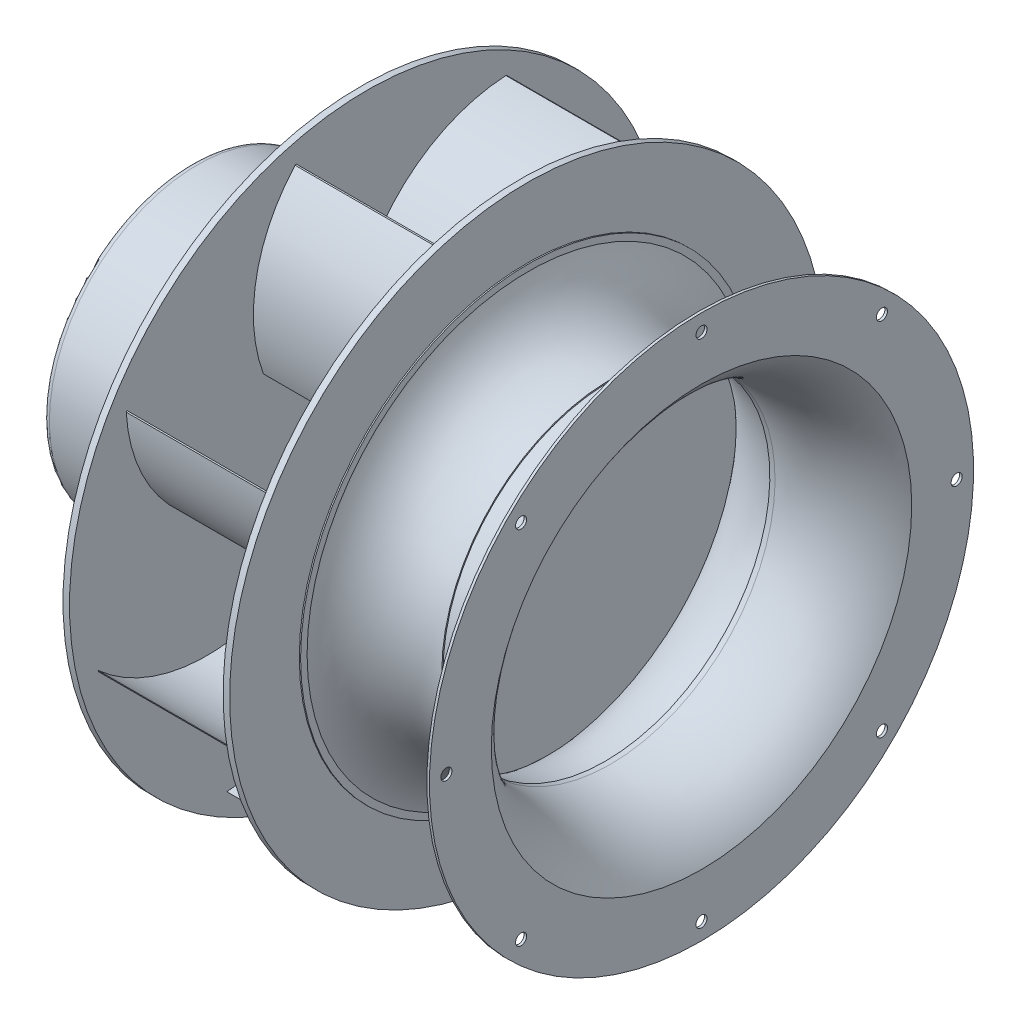
SolidWorks part; units mm, degrees
ref_plane "Front Plane" through (0, 0, 0) normal (0, 0, 1) x (1, 0, 0)
ref_plane "Top Plane" through (0, 0, 0) normal (0, 1, 0) x (1, 0, 0)
ref_plane "Right Plane" through (0, 0, 0) normal (1, 0, 0) x (0, 0, -1)
sketch "Sketch1" plane through (0, 0, 0) normal (0, 0, 1) x (1, 0, 0)
  line L0 (0, 0) -> (831.9083, 0) construction
  line L1 (0, 0) -> (0, 109)
  line L2 (5, 114) -> (70, 114)
  line L3 (70, 114) -> (70, 138)
  line L4 (70, 138) -> (90, 138)
  line L5 (90, 138) -> (90, 98)
  line L6 (90, 98) -> (95, 98)
  line L7 (95, 98) -> (95, 133)
  line L8 (95, 133) -> (105, 133)
  line L9 (105, 133) -> (105, 98)
  line L10 (105, 98) -> (130, 98)
  line L11 (130, 98) -> (130, 0)
  line L12 (130, 0) -> (0, 0)
  arc A0 (5, 114) -> (0, 109) centre (5, 109) ccw
  point P16 (0, 114)
  dimension "D10" = 5
  dimension "D1" = 114
  dimension "D2" = 24
  dimension "D3" = 70
  dimension "D4" = 40
  dimension "D5" = 35
  dimension "D6" = 5
  dimension "D7" = 20
  dimension "D8" = 10
  dimension "D9" = 60
revolve "Revolve1" add sketch "Sketch1" angle 360 about L0
sketch "Sketch2" plane through (130, 0, 0) normal (1, 0, 0) x (0, 0, -1)
  circle A0 centre (0, 0) radius 228.5
  dimension "D1" = 457
extrude "Extrude1" add sketch "Sketch2" along normal blind 5
sketch "Sketch9" plane through (130, 0, 0) normal (-1, 0, 0) x (0, 0, 1)
  circle A0 centre (0, 0) radius 223.5
  circle A1 centre (0, 0) radius 100
  circle A2 centre (0, 0) radius 228.5 construction
  dimension "D1" = 5
  dimension "D2" = 200
extrude "Extrude7" cut sketch "Sketch9" against normal blind 3
ref_plane "Plane1" through (253, 0, 0) normal (1, 0, 0) x (0, 0, -1)
sketch "Sketch3" plane through (253, 0, 0) normal (1, 0, 0) x (0, 0, -1)
  circle A0 centre (0, 0) radius 228.5
  dimension "D1" = 457
extrude "Extrude2" add sketch "Sketch3" along normal blind 5 separate body
sketch "Sketch4" plane through (135, 0, 0) normal (1, 0, 0) x (0, 0, -1)
  line L0 (0, 0) -> (0, 213.5) construction
  line L1 (0, 0) -> (114.25, 197.8868) construction
  line L2 (0, 112.5) -> (0.866, 112)
  line L3 (106.75, 184.8964) -> (107.616, 184.3964)
  circle A0 centre (0, 0) radius 213.5 construction
  circle A1 centre (0, 0) radius 228.5 construction
  circle A2 centre (0, 0) radius 112.5 construction
  arc A3 (0, 112.5) -> (106.75, 184.8964) centre (113.4764, 60.0775) cw
  arc A4 (0.866, 112) -> (107.616, 184.3964) centre (114.3424, 59.5775) cw
  dimension "D1" = 15
  dimension "D2" = 225
  dimension "D6" = 125
  dimension "D7" = 125
  dimension "D3" = 30
  dimension "D4" = 60
  dimension "D5" = 1
extrude "Extrude3" add sketch "Sketch4" along normal up to surface (123 mm away) up to face at (258, 0, -228.5)
ref_axis "Axis1" through (253.5503, 0, 0) along (-1, 0, 0)
pattern_circular "CirPattern1" count 8 over 360 about axis through (253.5503, 0, 0) along (-1, 0, 0) of "Extrude3"
sketch "Sketch5" plane through (0, 0, 0) normal (0, 0, 1) x (1, 0, 0)
  line L0 (0, 0) -> (527.2916, 0) construction
  line L1 (253.5503, 0) -> (75.411, 0) construction
  line L2 (258, 175) -> (259, 175)
  line L3 (259, 175) -> (259, 170)
  line L4 (258, 175) -> (258, 170)
  line L5 (322, 129.5) -> (322, 128.5)
  line L6 (70, 138) -> (70, -138) construction
  line L7 (258, -228.5) -> (258, 228.5) construction
  arc A0 (259, 170) -> (322, 129.5) centre (315.8504, 189.184) ccw
  arc A1 (258, 170) -> (322, 128.5) centre (315.2005, 188.1135) ccw
  dimension "D7" = 60
  dimension "D8" = 60
  dimension "D1" = 128.5
  dimension "D2" = 1
  dimension "D3" = 1
  dimension "D4" = 5
  dimension "D5" = 175
  dimension "D6" = 252
revolve "Revolve2" add sketch "Sketch5" angle 360 about L0
ref_plane "Plane3" through (392, 0, 0) normal (1, 0, 0) x (0, 0, -1)
sketch "Sketch6" plane through (0, 0, 0) normal (0, 0, 1) x (1, 0, 0)
  line L0 (392, 209) -> (390, 209)
  line L1 (392, -251.35) -> (392, 251.35) construction
  line L2 (390, 209) -> (390, 161.5)
  line L3 (0, 0) -> (615.1417, 0) construction
  line L4 (0, 114) -> (0, -114) construction
  line L5 (253.5503, 0) -> (75.411, 0) construction
  line L6 (392, 209) -> (392, 161.5)
  line L7 (318, 128.5) -> (322, 128.5)
  line L8 (318, 128.5) -> (318, 126.5)
  line L9 (318, 126.5) -> (322, 126.5)
  arc A0 (322, 128.5) -> (390, 161.5) centre (325.2152, 208.4354) ccw
  arc A1 (322, 126.5) -> (392, 161.5) centre (325.795, 206.4099) ccw
  dimension "D7" = 80
  dimension "D8" = 80
  dimension "D1" = 209
  dimension "D2" = 2
  dimension "D3" = 161.5
  dimension "D4" = 74
  dimension "D5" = 128.5
  dimension "D6" = 4
revolve "Revolve3" add sketch "Sketch6" angle 360 about L3
sketch "Sketch7" plane through (392, 0, 0) normal (1, 0, 0) x (0, 0, -1)
  line L0 (0, 0) -> (0, 196) construction
  circle A0 centre (0, 0) radius 196 construction
  circle A1 centre (0, 196) radius 4.25
  dimension "D1" = 392
  dimension "D2" = 8.5
extrude "Extrude5" cut sketch "Sketch7" against normal blind 5
pattern_circular "CirPattern2" count 8 over 360 about axis through (253.5503, 0, 0) along (-1, 0, 0) of "Extrude5"
sketch "Sketch8" plane through (0, 0, 0) normal (1, 0, 0) x (0, 0, -1)
  line L0 (0, 0) -> (0, 126) construction
  circle A0 centre (0, 0) radius 126 construction
  circle A1 centre (0, 126) radius 5
  dimension "D1" = 252
  dimension "D2" = 10
extrude "Extrude6" cut sketch "Sketch8" along normal up to surface (90 mm away) up to face at (90, 0, 138)
pattern_circular "CirPattern3" count 8 over 360 about axis through (253.5503, 0, 0) along (-1, 0, 0) of "Extrude6"
